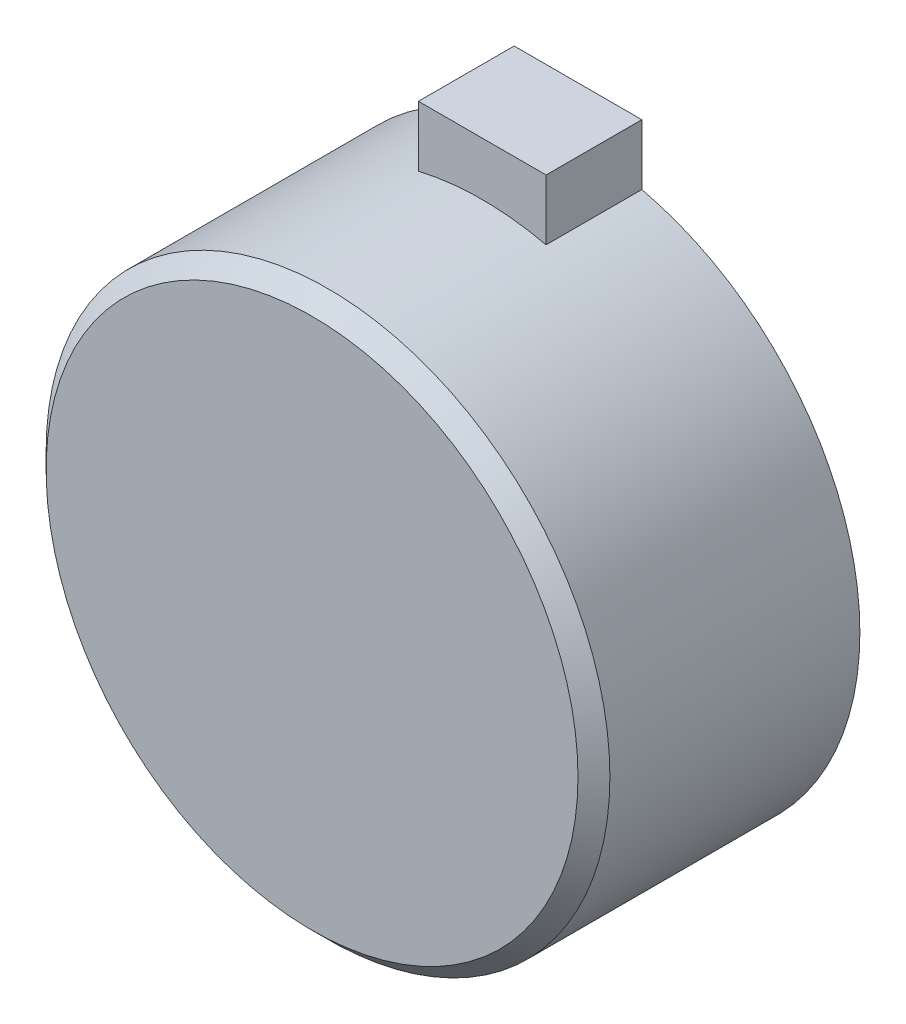
SolidWorks part; units mm, degrees
ref_plane "Front Plane" through (0, 0, 0) normal (0, 0, 1) x (1, 0, 0)
ref_plane "Top Plane" through (0, 0, 0) normal (0, 1, 0) x (1, 0, 0)
ref_plane "Right Plane" through (0, 0, 0) normal (1, 0, 0) x (0, 0, -1)
sketch "SK_Body" plane through (0, 0, 0) normal (0, 1, 0) x (1, 0, 0)
  line L0 (0, -10) -> (0, 60) construction
  line L1 (0, 0) -> (50, 0)
  line L2 (50, 0) -> (53, 3)
  line L3 (53, 3) -> (53, 50)
  line L4 (53, 50) -> (50, 50)
  line L5 (50, 50) -> (0, 50)
  line L6 (0, 50) -> (0, 0)
  dimension "P1" = 10
  dimension "P2" = 60
  dimension "R_front" = 50
  dimension "P4" = 53
  dimension "P5" = 3
  dimension "R_body" = 53
  dimension "L_body" = 50
  dimension "P8" = 50
  dimension "P9" = 50
  dimension "P10" = 50
revolve "Housing_Body" add sketch "SK_Body" angle 360 about L0
ref_plane "PL_Rear" through (0, 0, -50) normal (0, 0, 1) x (1, 0, 0)
sketch "SK_RearHole" plane through (0, 0, -50) normal (0, 0, 1) x (1, 0, 0)
  circle A0 centre (43, 0) radius 1.65
  dimension "D_rh" = 3.3
  dimension "R_rh" = 43
extrude "Rear_Tapped_Hole" cut sketch "SK_RearHole" along normal blind 8
ref_axis "AX_Joint" through (0, 0, -52.5) along (0, 0, 1)
pattern_circular "Rear_Hole_Pattern" count 8 over 360 about axis through (0, 0, -52.5) along (0, 0, 1) of "Rear_Tapped_Hole"
sketch "SK_Connector" plane through (0, 0, -50) normal (0, 0, 1) x (1, 0, 0)
  line L0 (-12, 49) -> (12, 49)
  line L1 (12, 49) -> (12, 63)
  line L2 (12, 63) -> (-12, 63)
  line L3 (-12, 63) -> (-12, 49)
  dimension "P1" = 12
  dimension "P2" = 49
  dimension "P3" = 12
  dimension "P4" = 49
  dimension "P5" = 12
  dimension "P6" = 63
  dimension "P7" = 12
  dimension "P8" = 63
extrude "Connector_Zone" add sketch "SK_Connector" along normal blind 18
equation "\"D_act\" = 106"
equation "\"L_housing\" = 50"
equation "\"PCD_rear\" = 86"
equation "\"D_rear_hole\" = 3.3"
equation "\"D_bearing_boss\" = 64"
equation "\"R_front@SK_Body\" = \"D_act\"/2-3.0"
equation "\"R_body@SK_Body\" = \"D_act\"/2"
equation "\"L_body@SK_Body\" = \"L_housing\""
equation "\"D_rh@SK_RearHole\" = \"D_rear_hole\""
equation "\"R_rh@SK_RearHole\" = \"PCD_rear\"/2"
